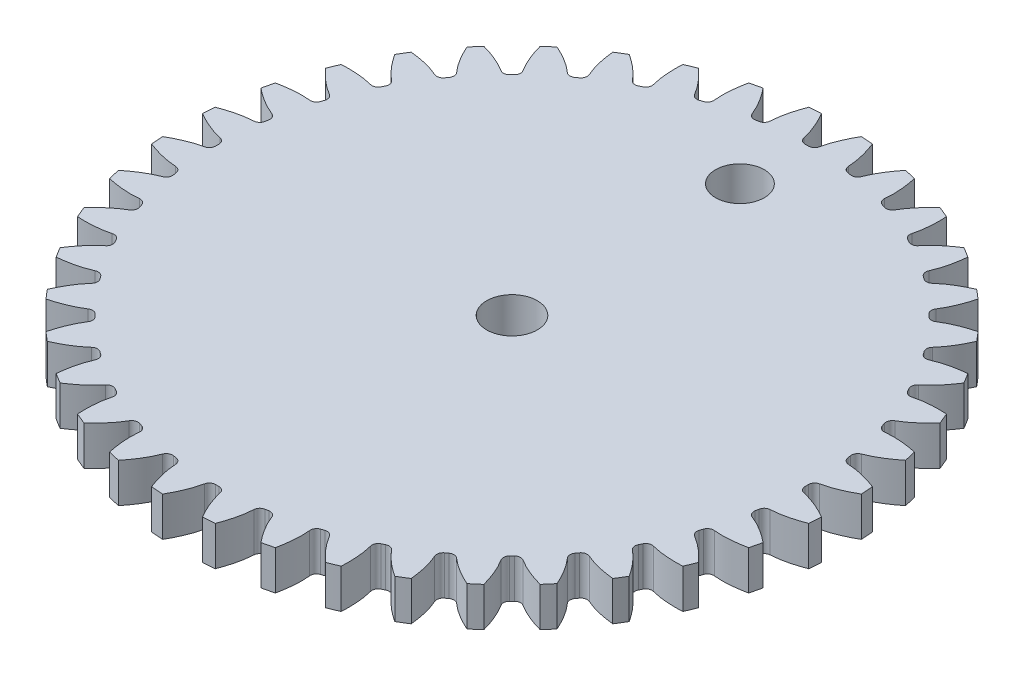
SolidWorks part; units mm, degrees
ref_plane "Front Plane" through (0, 0, 0) normal (0, 0, 1) x (1, 0, 0)
ref_plane "Top Plane" through (0, 0, 0) normal (0, 1, 0) x (1, 0, 0)
ref_plane "Right Plane" through (0, 0, 0) normal (1, 0, 0) x (0, 0, -1)
sketch "Sketch2" plane through (0, 0, 0) normal (0, 1, 0) x (1, 0, 0)
  circle A0 centre (0, 0) radius 53.34
  dimension "D1" = 106.68
extrude "Boss-Extrude1" add sketch "Sketch2" along normal blind 12.7
sketch "Sketch3" plane through (0, 0, 0) normal (0, -1, 0) x (-1, 0, 0)
  line L0 (0, 0) -> (47.7222, -1.163) construction
  line L1 (0, 0) -> (47.7222, 1.163) construction
  line L2 (47.7222, -1.163) -> (47.6109, -1.1603)
  line L3 (47.7222, 1.163) -> (47.6109, 1.1603)
  circle A0 centre (0, 0) radius 53.34
  circle A1 centre (0, 0) radius 50.8
  circle A2 centre (0, 0) radius 47.752
  circle A3 centre (0, 0) radius 47.625
  spline S0 degree 4 poles (47.7222, 1.163) (47.731, 1.1633) (47.7556, 1.1645) (47.802, 1.1678) (47.8777, 1.1747) (47.9741, 1.186) (48.0986, 1.2033) (48.2451, 1.2271) (48.4058, 1.257) (48.5805, 1.2934) (48.7546, 1.3332) (48.928, 1.3762) (49.1005, 1.4219) (49.3093, 1.4808) (49.5592, 1.5562) (49.8507, 1.6513) (50.1805, 1.7675) (50.5158, 1.8948) (50.845, 2.0273) (51.1768, 2.1695) (51.4972, 2.313) (51.8289, 2.4707) (52.1347, 2.6205) (52.4761, 2.7979) (52.7513, 2.9438) (53.113, 3.1463) (53.3263, 3.2689) (53.5754, 3.4159) (53.6857, 3.483) (53.7537, 3.5243) knots 0 0 0 0 0 0.005377 0.015084 0.028532 0.04661 0.064855 0.092111 0.119476 0.146842 0.174209 0.201575 0.228941 0.256307 0.307035 0.361767 0.4165 0.471232 0.525964 0.580697 0.635429 0.690161 0.744894 0.799626 0.854358 0.909091 0.954545 1 1 1 1 1 construction
  spline S1 degree 4 poles (47.7222, 1.163) (47.731, 1.1633) (47.7556, 1.1645) (47.802, 1.1678) (47.8777, 1.1747) (47.9741, 1.186) (48.0986, 1.2033) (48.2451, 1.2271) (48.4058, 1.257) (48.5805, 1.2934) (48.7546, 1.3332) (48.928, 1.3762) (49.1005, 1.4219) (49.3093, 1.4808) (49.5592, 1.5562) (49.8507, 1.6513) (50.1805, 1.7675) (50.5158, 1.8948) (50.845, 2.0273) (51.1768, 2.1695) (51.4972, 2.313) (51.8289, 2.4707) (52.1347, 2.6205) (52.4761, 2.7979) (52.7513, 2.9438) (53.0346, 3.1024) (53.1723, 3.1808) (53.2426, 3.2213) knots 0 0 0 0 0 0.005377 0.015084 0.028532 0.04661 0.064855 0.092111 0.119476 0.146842 0.174209 0.201575 0.228941 0.256307 0.307035 0.361767 0.4165 0.471232 0.525964 0.580697 0.635429 0.690161 0.744894 0.799626 0.854358 0.909091 0.909091 0.909091 0.909091 0.909091
  spline S2 degree 4 poles (47.7222, -1.163) (47.731, -1.1633) (47.7556, -1.1645) (47.802, -1.1678) (47.8777, -1.1747) (47.9741, -1.186) (48.0986, -1.2033) (48.2451, -1.2271) (48.4058, -1.257) (48.5805, -1.2934) (48.7546, -1.3332) (48.928, -1.3762) (49.1005, -1.4219) (49.3093, -1.4808) (49.5592, -1.5562) (49.8507, -1.6513) (50.1805, -1.7675) (50.5158, -1.8948) (50.845, -2.0273) (51.1768, -2.1695) (51.4972, -2.313) (51.8289, -2.4707) (52.1347, -2.6205) (52.4761, -2.7979) (52.7513, -2.9438) (53.113, -3.1463) (53.3263, -3.2689) (53.5754, -3.4159) (53.6857, -3.483) (53.7537, -3.5243) knots 0 0 0 0 0 0.005377 0.015084 0.028532 0.04661 0.064855 0.092111 0.119476 0.146842 0.174209 0.201575 0.228941 0.256307 0.307035 0.361767 0.4165 0.471232 0.525964 0.580697 0.635429 0.690161 0.744894 0.799626 0.854358 0.909091 0.954545 1 1 1 1 1 construction
  spline S3 degree 4 poles (47.7222, -1.163) (47.731, -1.1633) (47.7556, -1.1645) (47.802, -1.1678) (47.8777, -1.1747) (47.9741, -1.186) (48.0986, -1.2033) (48.2451, -1.2271) (48.4058, -1.257) (48.5805, -1.2934) (48.7546, -1.3332) (48.928, -1.3762) (49.1005, -1.4219) (49.3093, -1.4808) (49.5592, -1.5562) (49.8507, -1.6513) (50.1805, -1.7675) (50.5158, -1.8948) (50.845, -2.0273) (51.1768, -2.1695) (51.4972, -2.313) (51.8289, -2.4707) (52.1347, -2.6205) (52.4761, -2.7979) (52.7513, -2.9438) (53.0346, -3.1024) (53.1723, -3.1808) (53.2426, -3.2213) knots 0 0 0 0 0 0.005377 0.015084 0.028532 0.04661 0.064855 0.092111 0.119476 0.146842 0.174209 0.201575 0.228941 0.256307 0.307035 0.361767 0.4165 0.471232 0.525964 0.580697 0.635429 0.690161 0.744894 0.799626 0.854358 0.909091 0.909091 0.909091 0.909091 0.909091
  dimension "D1" = 106.68
  dimension "D2" = 101.6
  dimension "D3" = 95.504
  dimension "D4" = 95.25
extrude "Cut-Extrude1" cut sketch "Sketch3" against normal blind 12.7 contours A1 S3 A0 S1 | A2 S3 A1 S1 | L2 S3 A2 S1 L3 A3 region at (-47.6838, 0, 0) region at (-49.4115, 0, 0) region at (-52.1487, 0, 0)
fillet "Fillet2" radius 1.016 2 edges at (-47.6109, 6.35, -1.1603) (-47.6109, 6.35, 1.1603)
pattern_circular "CirPattern1" count 40 over 360 about axis through (0, 12.7, 0) along (0, 1, 0) of "Fillet2", "Cut-Extrude1"
sketch "Sketch4" plane through (0, 12.7, 0) normal (0, 1, 0) x (1, 0, 0)
  circle A0 centre (0, 0) radius 4.0957
  dimension "D1" = 8.1915
extrude "Cut-Extrude2" cut sketch "Sketch4" against normal through all
sketch "Sketch5" plane through (0, 12.7, 0) normal (0, 1, 0) x (1, 0, 0)
  line L1 (0, 7.3763) -> (-6.3881, 3.6882)
  line L2 (-6.3881, 3.6882) -> (-6.3881, -3.6882)
  line L3 (-6.3881, -3.6882) -> (0, -7.3763)
  line L4 (0, -7.3763) -> (6.3881, -3.6882)
  line L5 (6.3881, -3.6882) -> (6.3881, 3.6882)
  line L6 (6.3881, 3.6882) -> (0, 7.3763)
  circle A0 centre (0, 0) radius 6.3881 construction
  dimension "D1" = 12.7762
extrude "Cut-Extrude3" cut sketch "Sketch5" against normal blind 6.35
sketch "Sketch6" plane through (0, 12.7, 0) normal (0, 1, 0) x (1, 0, 0)
  line L0 (0, 0) -> (0, 36.83) construction
  circle A0 centre (0, 36.83) radius 3.937
  dimension "D2" = 7.874
  dimension "D1" = 36.83
extrude "Cut-Extrude4" cut sketch "Sketch6" against normal through all both and the other way through all
sketch "Sketch7" plane through (0, 6.35, 0) normal (0, 1, 0) x (1, 0, 0)
  circle A0 centre (0, 0) radius 100.3623
extrude "Cut-Extrude6" cut sketch "Sketch7" along normal through all
equation "\"DiametralPitch\"= 10"
equation "\"NumTeeth\"= 40"
equation "\"PressureAngle\"= 20deg"
equation "\"Addendum\"= 1 / \"DiametralPitch\""
equation "\"Dedendum\"= 1.25 / \"DiametralPitch\""
equation "\"WorkingDepth\"= 2 / \"DiametralPitch\""
equation "\"WholeDepth\"= 2.25 / \"DiametralPitch\""
equation "\"Clearance\"= 0.3 / \"DiametralPitch\""
equation "\"ToothThickness\"= 1.5708 / \"DiametralPitch\""
equation "\"CircularPitch\"= pi / \"DiametralPitch\""
equation "\"PitchCircle\"= \"NumTeeth\" / \"DiametralPitch\""
equation "\"OutsideDiameter\"= ( \"NumTeeth\" + 2 ) / \"DiametralPitch\""
equation "\"Fillet\"= \"Clearance\" * cos ( \"PressureAngle\" ) * tan ( ( 90 + \"PressureAngle\" ) / 2 )"
equation "\"AddendumCircle\"= \"PitchCircle\" + ( 2 * \"Addendum\" )"
equation "\"DedendumCircle\"= \"PitchCircle\" - ( 2 * \"Dedendum\" )"
equation "\"BaseCircle\"= \"PitchCircle\" * cos ( \"PressureAngle\" )"
equation "\"PitchAngle\"= 360deg / \"NumTeeth\""
equation "\"Alpha\"= sqr ( \"PitchCircle\" ^ 2 - \"BaseCircle\" ^ 2 ) / \"BaseCircle\" * 180 / PI - \"PressureAngle\""
equation "\"Beta\"= ( \"PitchAngle\" / 4 - \"Alpha\" )"
equation "\"Phi\"= sqr ( ( \"AddendumCircle\" / 2 ) ^ 2 - ( \"BaseCircle\" / 2 ) ^ 2 ) / ( \"BaseCircle\" / 2 )"
